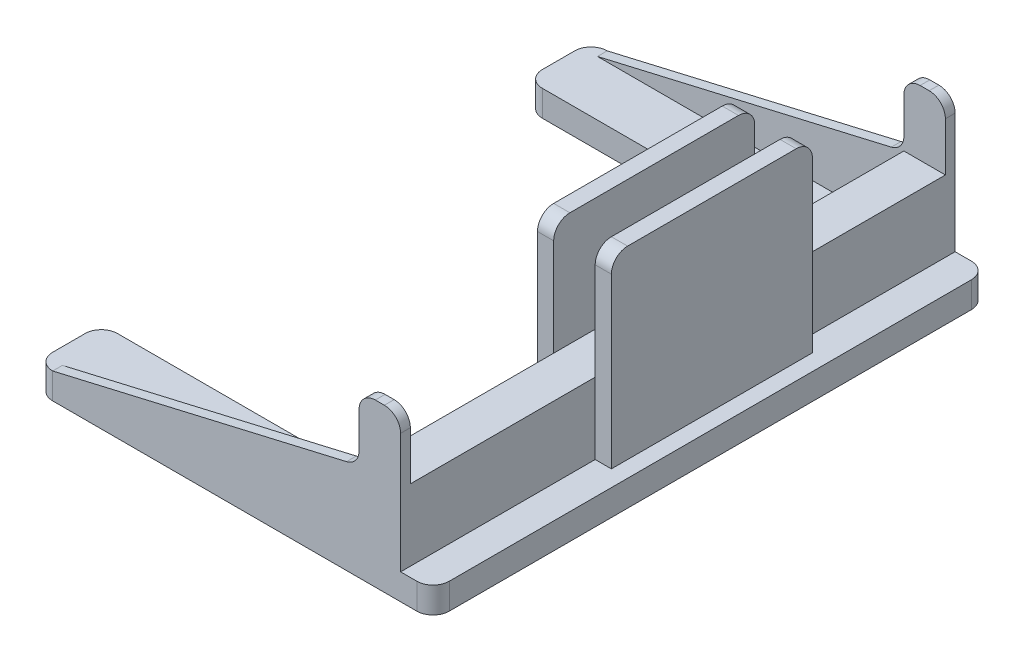
SolidWorks part; units mm, degrees
ref_plane "Přední rovina" through (0, 0, 0) normal (0, 0, 1) x (1, 0, 0)
ref_plane "Horní rovina" through (0, 0, 0) normal (0, 1, 0) x (1, 0, 0)
ref_plane "Pravá rovina" through (0, 0, 0) normal (1, 0, 0) x (0, 0, -1)
sketch "Skica1" plane through (0, 0, 0) normal (0, 0, 1) x (1, 0, 0)
  line L0 (-27.8, 65) -> (-27.8, 8)
  line L1 (-27.8, 8) -> (-122.3, 8)
  line L2 (-122.3, 8) -> (-122.3, 0)
  line L3 (-122.3, 0) -> (0, 0)
  line L4 (0, 0) -> (0, 8)
  line L5 (0, 8) -> (-5, 8)
  line L6 (-5, 8) -> (-5, 65)
  line L7 (-5, 65) -> (-10, 65)
  line L8 (-10, 65) -> (-10, 30)
  line L9 (-10, 30) -> (-22.8, 30)
  line L10 (-22.8, 30) -> (-22.8, 65)
  line L11 (-22.8, 65) -> (-27.8, 65)
  dimension "D1" = 12.8
  dimension "D2" = 5
  dimension "D3" = 5
  dimension "D4" = 8
  dimension "D5" = 5
  dimension "D6" = 94.5
  dimension "D7" = 35
  dimension "D8" = 30
extrude "Přidat vysunutím1" add sketch "Skica1" along normal mid plane 171
sketch "Skica2" plane through (-27.8, 0, 0) normal (-1, 0, 0) x (0, 0, 1)
  line L1 (-85.5, 65) -> (-36.5, 65)
  line L2 (-85.5, 65) -> (-85.5, 30)
  line L3 (-85.5, 30) -> (-36.5, 30)
  line L4 (-36.5, 65) -> (-36.5, 30)
  line L5 (85.5, 30) -> (-85.5, 30) construction
  line L6 (85.5, 65) -> (25.5, 65)
  line L7 (85.5, 65) -> (85.5, 30)
  line L8 (85.5, 30) -> (25.5, 30)
  line L9 (25.5, 65) -> (25.5, 30)
  dimension "D1" = 60
  dimension "D2" = 49
extrude "Odebrat vysunutím1" cut sketch "Skica2" against normal through all
sketch "Skica3" plane through (0, 30, 0) normal (0, 1, 0) x (1, 0, 0)
  line L1 (-22.8, 36.5) -> (-27.8, 36.5)
  line L2 (-22.8, 36.5) -> (-22.8, 85.5)
  line L3 (-22.8, 85.5) -> (-27.8, 85.5)
  line L4 (-27.8, 36.5) -> (-27.8, 85.5)
  line L5 (-10, 36.5) -> (-5, 36.5)
  line L6 (-10, 36.5) -> (-10, 85.5)
  line L7 (-10, 85.5) -> (-5, 85.5)
  line L8 (-5, 36.5) -> (-5, 85.5)
  line L9 (-22.8, -25.5) -> (-27.8, -25.5)
  line L10 (-22.8, -25.5) -> (-22.8, -85.5)
  line L11 (-22.8, -85.5) -> (-27.8, -85.5)
  line L12 (-27.8, -25.5) -> (-27.8, -85.5)
  line L13 (-10, -25.5) -> (-5, -25.5)
  line L14 (-10, -25.5) -> (-10, -85.5)
  line L15 (-10, -85.5) -> (-5, -85.5)
  line L16 (-5, -25.5) -> (-5, -85.5)
extrude "Odebrat vysunutím2" cut sketch "Skica3" against normal up to surface (22 mm away) up to face at (-75.05, 8, 0)
sketch "Skica4" plane through (0, 8, 0) normal (0, 1, 0) x (1, 0, 0)
  line L0 (-122.3, -85.5) -> (-122.3, 85.5) construction
  line L1 (-122.3, 65.5) -> (-27.8, 65.5)
  line L2 (-122.3, 65.5) -> (-122.3, -65.5)
  line L3 (-122.3, -65.5) -> (-27.8, -65.5)
  line L4 (-27.8, 65.5) -> (-27.8, -65.5)
  line L5 (-22.8, 85.5) -> (-122.3, 85.5) construction
  line L6 (-27.8, -25.5) -> (-27.8, 36.5) construction
  point P6 (-122.3, 0)
  point P7 (-122.3, 0)
  dimension "D1" = 20
extrude "Odebrat vysunutím3" cut sketch "Skica4" against normal through all
fillet "Zaoblit1" radius 5 6 edges at (0, 4, -85.5) (0, 4, 85.5) (-122.3, 4, 85.5) (-122.3, 4, 65.5) (-122.3, 4, -85.5) (-122.3, 4, -65.5)
fillet "Zaoblit2" radius 20 2 edges at (-27.8, 4, 65.5) (-27.8, 4, -65.5)
fillet "Zaoblit3" radius 5 4 edges at (-25.3, 65, 25.5) (-7.5, 65, 25.5) (-25.3, 65, -36.5) (-7.5, 65, -36.5)
sketch "Skica5" plane through (0, 0, -85.5) normal (0, 0, -1) x (-1, 0, 0)
  line L0 (22.8, 30) -> (22.8, 8)
  line L1 (22.8, 8) -> (117.3, 8)
  line L2 (117.3, 8) -> (22.8, 30)
extrude "Přidat vysunutím2" add sketch "Skica5" against normal blind 3
mirror "Zrcadlit1" about plane through (0, 0, 0) normal (0, 0, 1) of "Přidat vysunutím2"
sketch "Skica6" plane through (0, 30, 0) normal (0, 1, 0) x (1, 0, 0)
  line L1 (-22.8, 82.5) -> (-10, 82.5)
  line L2 (-22.8, 82.5) -> (-22.8, 85.5)
  line L3 (-22.8, 85.5) -> (-10, 85.5)
  line L4 (-10, 82.5) -> (-10, 85.5)
  line L5 (-22.8, -82.5) -> (-10, -82.5)
  line L6 (-22.8, -82.5) -> (-22.8, -85.5)
  line L7 (-22.8, -85.5) -> (-10, -85.5)
  line L8 (-10, -82.5) -> (-10, -85.5)
extrude "Přidat vysunutím3" add sketch "Skica6" along normal blind 20
fillet "Zaoblit4" radius 5 6 edges at (-10, 50, 84) (-22.8, 30, 84) (-22.8, 50, 84) (-10, 50, -84) (-22.8, 50, -84) (-22.8, 30, -84)
